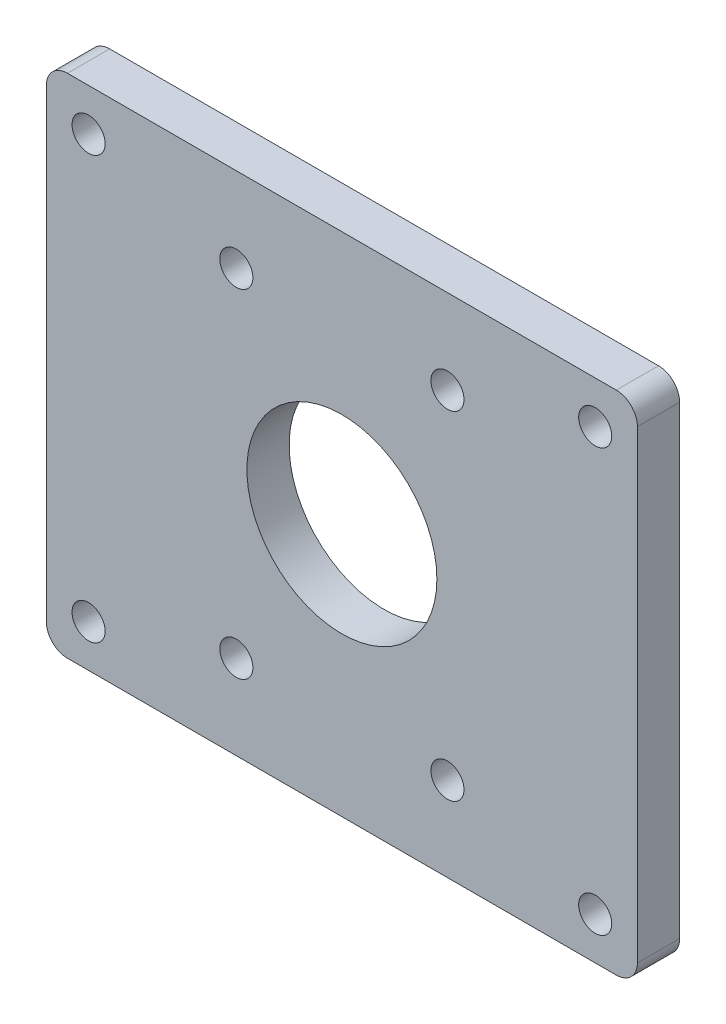
SolidWorks part; units mm, degrees
material "6061-T6 (SS)"
ref_plane "Front Plane" through (0, 0, 0) normal (0, 0, 1) x (1, 0, 0)
ref_plane "Top Plane" through (0, 0, 0) normal (0, 1, 0) x (1, 0, 0)
ref_plane "Right Plane" through (0, 0, 0) normal (1, 0, 0) x (0, 0, -1)
sketch "Sketch1" plane through (0, 0, 0) normal (0, 0, 1) x (1, 0, 0)
  line L8 (-38.1, -31.75) -> (-38.1, 31.75) construction
  line L9 (-44.45, -38.1) -> (44.45, -38.1)
  line L10 (-44.45, -38.1) -> (-44.45, 38.1)
  line L11 (-44.45, 38.1) -> (44.45, 38.1)
  line L12 (44.45, -38.1) -> (44.45, 38.1)
  line L13 (-44.45, -38.1) -> (44.45, 38.1) construction
  line L14 (-44.45, 38.1) -> (44.45, -38.1) construction
  line L19 (-37.0417, -31.75) -> (37.0417, 31.75) construction
  line L20 (-59.6943, 51.1665) -> (37.0417, -31.75) construction
  line L21 (-25.4, -38.1) -> (25.4, -38.1) construction
  line L22 (-25.4, -38.1) -> (-25.4, 38.1) construction
  line L23 (-25.4, 38.1) -> (25.4, 38.1) construction
  line L24 (25.4, -38.1) -> (25.4, 38.1) construction
  line L25 (-25.4, -38.1) -> (25.4, 38.1) construction
  line L26 (-25.4, 38.1) -> (25.4, -38.1) construction
  line L27 (-38.1, 31.75) -> (38.1, 31.75) construction
  line L28 (38.1, -31.75) -> (38.1, 31.75) construction
  line L29 (-38.1, -31.75) -> (38.1, -31.75) construction
  circle A8 centre (0, 0) radius 30 construction
  circle A9 centre (0, 0) radius 14.2875
  circle A11 centre (0, 0) radius 9.5758 construction
  circle A12 centre (0, 0) radius 11.5062 construction
  circle A13 centre (-15.875, -25.4) radius 2.4892
  circle A14 centre (15.875, -25.4) radius 2.4892
  circle A15 centre (15.875, 25.4) radius 2.4892
  circle A16 centre (-15.875, 25.4) radius 2.4892
  circle A17 centre (-38.1, 31.75) radius 2.4892
  circle A21 centre (-38.1, -31.75) radius 2.4892
  circle A22 centre (38.1, -31.75) radius 2.4892
  circle A23 centre (38.1, 31.75) radius 2.4892
  point P0 (0, 0)
  point P6 (0, 0)
  dimension "D4" = 28.575
  dimension "D3" = 4.9784
  dimension "D5" = 60
  dimension "D7" = 19.1516
  dimension "D8" = 23.0124
  dimension "D10" = 2
  dimension "D11" = 31.75
  dimension "D12" = 50.8
  dimension "D1" = 88.9
  dimension "D2" = 6.35
  dimension "D6" = 50.8
  dimension "D9" = 2
  dimension "D13" = 15.875
  dimension "D14" = 25.4
  dimension "D15" = 76.2
extrude "Boss-Extrude1" add sketch "Sketch1" along normal blind 6.35
fillet "Fillet1" radius 3.175 4 edges at (44.45, -38.1, 3.175) (-44.45, -38.1, 3.175) (-44.45, 38.1, 3.175) (44.45, 38.1, 3.175)
